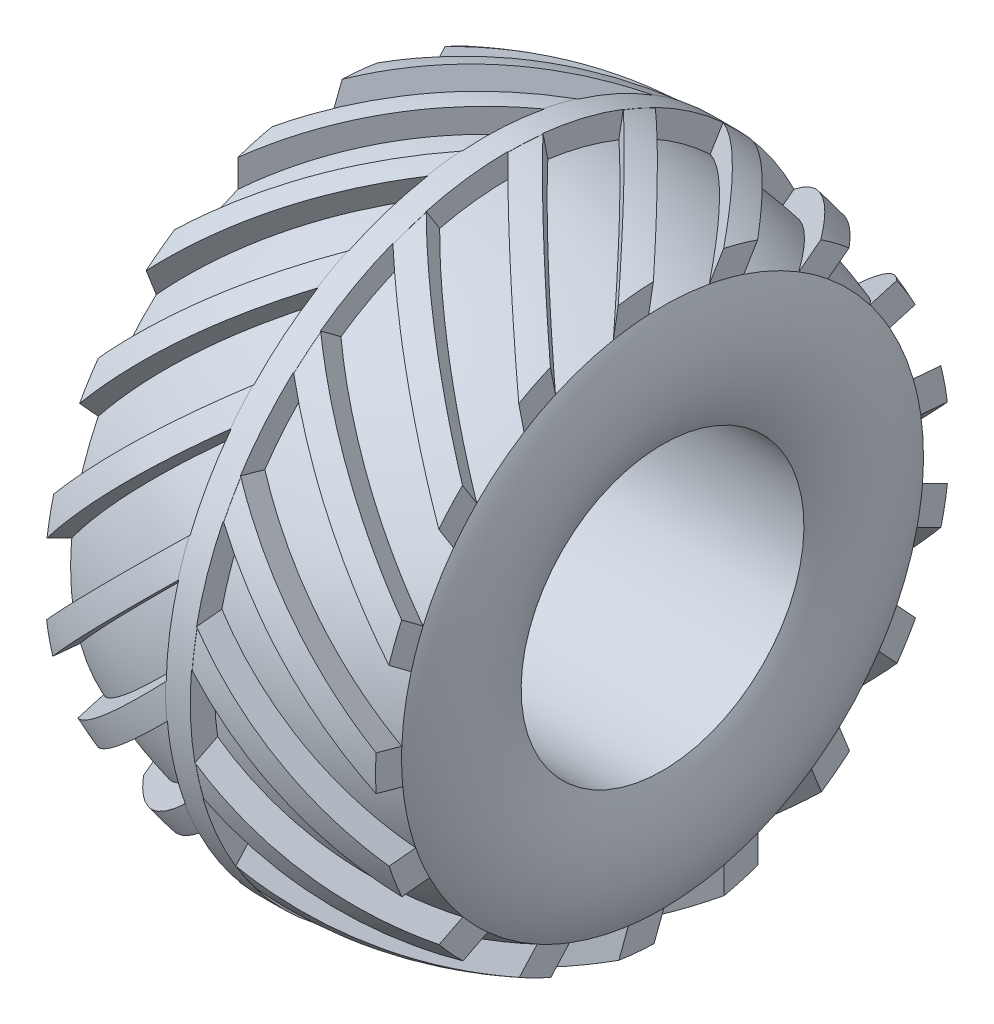
SolidWorks part; units mm, degrees
material "Rubber"
ref_plane "Front Plane" through (0, 0, 0) normal (0, 0, 1) x (1, 0, 0)
ref_plane "Top Plane" through (0, 0, 0) normal (0, 1, 0) x (1, 0, 0)
ref_plane "Right Plane" through (0, 0, 0) normal (1, 0, 0) x (0, 0, -1)
sketch "Sketch1" plane through (0, 0, 0) normal (0, 0, 1) x (1, 0, 0)
  line L0 (0, 0) -> (41.3801, 0) construction
  line L1 (-27.5, 23.5) -> (27.5, 23.5)
  line L2 (0, 23.5) -> (0, 0) construction
  line L3 (-27.5, 43.372) -> (27.5, 43.372) construction
  line L4 (-27.5, 23.5) -> (-27.5, -27.6884) construction
  line L5 (0, 43.372) -> (0, 23.5) construction
  line L6 (0, 43.372) -> (0, 91.8051) construction
  line L7 (-2, 53) -> (2, 53)
  line L8 (2, 53) -> (2, 48.9714)
  line L10 (-2, 48.9714) -> (-2, 53)
  arc A0 (27.5, 43.372) -> (27.5, 23.5) centre (9.0052, 33.436) cw
  arc A1 (-27.5, 43.372) -> (-2, 48.9714) centre (0, -21) cw
  arc A2 (-27.5, 43.372) -> (-27.5, 23.5) centre (-9.0052, 33.436) ccw
  arc A3 (2, 48.9714) -> (27.5, 43.372) centre (0, -21) cw
  point P17 (0, 53)
  dimension "D3" = 49
  dimension "D4" = 60
  dimension "D5" = 55
  dimension "D6" = 70
  dimension "D1" = 55
  dimension "D2" = 23.5
  dimension "D7" = 4
  dimension "D8" = 4
revolve "Revolve1" add sketch "Sketch1" angle 360 about L0
ref_plane "Plane1" through (0, 30, 0) normal (0, 1, 0) x (1, 0, 0)
sketch "Sketch2" plane through (0, 30, 0) normal (0, 1, 0) x (1, 0, 0)
  line L0 (0, 0) -> (54.0828, 0) construction
  line L1 (2, 15.5784) -> (27.5, -9.9216)
  line L2 (2, -48.9714) -> (2, 48.9714) construction
  line L3 (27.5, -43.372) -> (27.5, 43.372) construction
  line L4 (27.5, -9.9216) -> (27.5, -15.5784)
  line L5 (27.5, -15.5784) -> (2, 9.9216)
  line L6 (2, 9.9216) -> (2, 15.5784)
  line L7 (2, 15.5784) -> (2, 0) construction
  line L8 (27.5, -15.5784) -> (27.5, 0) construction
  line L9 (0, 0) -> (0, 60.4891) construction
  line L10 (-27.5, -15.5784) -> (-27.5, 0) construction
  line L11 (-2, 15.5784) -> (-2, 0) construction
  line L12 (0, 0) -> (-54.0828, 0) construction
  line L13 (-2, 9.9216) -> (-2, 15.5784)
  line L14 (-27.5, -15.5784) -> (-2, 9.9216)
  line L15 (-27.5, -9.9216) -> (-27.5, -15.5784)
  line L16 (-2, 15.5784) -> (-27.5, -9.9216)
  dimension "D1" = 4
  dimension "D2" = 45
extrude "Boss-Extrude1" add sketch "Sketch2" along normal up to surface (22.0631 mm away) up to face at (-2, 0, 53)
pattern_circular "CirPattern1" count 17 over 360 about axis through (-27.5, 0, 0) along (-1, 0, 0) of "Boss-Extrude1"
sketch "Sketch3" plane through (0, 0, 0) normal (0, 0, 1) x (1, 0, 0)
  line L0 (-29.0714, 47.0504) -> (-29.0714, 58.2289)
  line L1 (-29.0714, 58.2289) -> (-2.1143, 58.2289)
  line L2 (-2.1143, 58.2289) -> (-2.1143, 52.9698)
  line L3 (2.1143, 52.9698) -> (2.1143, 58.2289)
  line L4 (2.1143, 58.2289) -> (29.0714, 58.2289)
  line L5 (29.0714, 58.2289) -> (29.0714, 47.0504)
  line L6 (-200000, 0) -> (200041.3801, 0) construction
  line L7 (-200000, 0) -> (200041.3801, 0) construction
  arc A0 (27.5, 43.372) -> (2, 48.9714) centre (0, -21) ccw construction
  arc A1 (-2, 48.9714) -> (-27.5, 43.372) centre (0, -21) ccw construction
  arc A2 (-2, 48.9714) -> (-27.5, 43.372) centre (0, -21) ccw construction
  arc A3 (27.5, 43.372) -> (2, 48.9714) centre (0, -21) ccw construction
  arc A4 (-2.1143, 52.9698) -> (-29.0714, 47.0504) centre (0, -21) ccw
  arc A5 (29.0714, 47.0504) -> (2.1143, 52.9698) centre (0, -21) ccw
  dimension "D1" = 4
revolve "Cut-Revolve1" cut sketch "Sketch3" angle 360 about L7
split "Split1" trim tools "Right Plane" bodies to split 104 resulting bodies 105 106
move or copy body "Body-Move/Copy2" bodies to move or copy 105 copy no rotation origin (0, 0, 0) rotation axis (1, 0, 0) rotation angle 11
combine bodies "Combine2" operation type add bodies to combine 109 106
